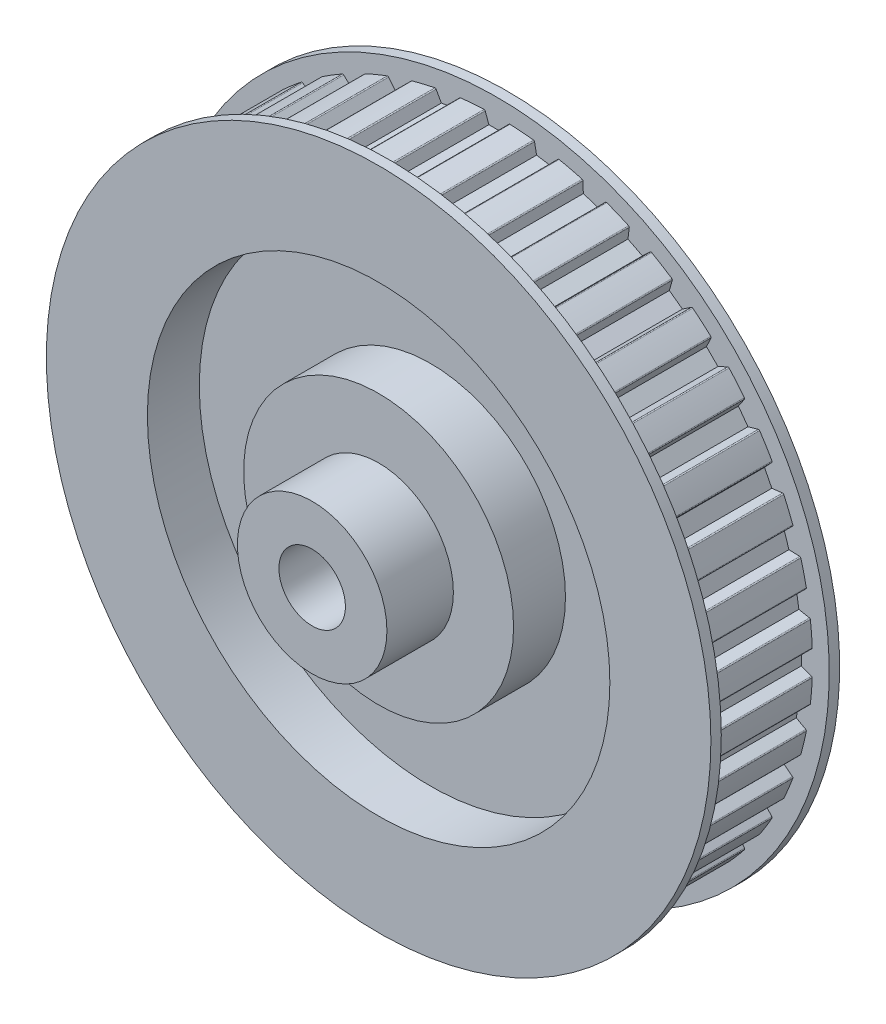
SolidWorks part; units mm, degrees
material "Nylon 101"
ref_plane "Front Plane" through (0, 0, 0) normal (0, 0, 1) x (1, 0, 0)
ref_plane "Top Plane" through (0, 0, 0) normal (0, 1, 0) x (1, 0, 0)
ref_plane "Right Plane" through (0, 0, 0) normal (1, 0, 0) x (0, 0, -1)
sketch "Sketch1" plane through (0, 0, 0) normal (0, 1, 0) x (1, 0, 0)
  line L0 (63.5, -10.3187) -> (0, -10.3187)
  line L1 (0, -10.3187) -> (0, -12.3031)
  line L2 (0, -12.3031) -> (63.5, -12.3031)
  line L3 (63.5, -12.3031) -> (63.5, -10.3187)
  line L4 (0, -10.3187) -> (0, -12.3031) construction
  dimension "D1" = 63.5
  dimension "D2" = 1.9844
revolve "Revolve1" add sketch "Sketch1" angle 360 about L4 reverse direction yes
sketch "Sketch2" plane through (0, 0, 10.3187) normal (0, 0, -1) x (-1, 0, 0)
  line L0 (20.8148, -56.5864) -> (19.4459, -54.8343)
  line L1 (19.4459, -54.8343) -> (16.4988, -55.7919)
  line L2 (16.4988, -55.7919) -> (16.4212, -58.014)
  line L3 (-25.2944, -54.7309) -> (-25.0234, -52.524)
  line L4 (-25.0234, -52.524) -> (-27.7845, -51.1172)
  line L5 (-27.7845, -51.1172) -> (-29.4106, -52.6336)
  line L6 (-52.6336, -29.4106) -> (-51.1172, -27.7845)
  line L7 (-51.1172, -27.7845) -> (-52.524, -25.0234)
  line L8 (-52.524, -25.0234) -> (-54.7309, -25.2944)
  line L9 (-58.014, 16.4212) -> (-55.7919, 16.4988)
  line L10 (-55.7919, 16.4988) -> (-54.8343, 19.4459)
  line L11 (-54.8343, 19.4459) -> (-56.5864, 20.8148)
  line L12 (-37.2822, 47.3848) -> (-35.4389, 46.1414)
  line L13 (-35.4389, 46.1414) -> (-32.9319, 47.9629)
  line L14 (-32.9319, 47.9629) -> (-33.5448, 50.1002)
  line L15 (7.1436, 59.8686) -> (7.5678, 57.686)
  line L16 (7.5678, 57.686) -> (10.6285, 57.2012)
  line L17 (10.6285, 57.2012) -> (11.7064, 59.1459)
  line L18 (40.9692, 44.2358) -> (40.0295, 42.2207)
  line L19 (40.0295, 42.2207) -> (42.2207, 40.0295)
  line L20 (42.2207, 40.0295) -> (44.2358, 40.9692)
  line L21 (59.1459, 11.7064) -> (57.2012, 10.6285)
  line L22 (57.2012, 10.6285) -> (57.686, 7.5678)
  line L23 (57.686, 7.5678) -> (59.8686, 7.1436)
  line L24 (50.1002, -33.5448) -> (47.9629, -32.9319)
  line L25 (47.9629, -32.9319) -> (46.1414, -35.4389)
  line L26 (46.1414, -35.4389) -> (47.3848, -37.2822)
  arc A0 (47.3848, -37.2822) -> (20.8148, -56.5864) centre (0, 0) cw
  arc A1 (16.4212, -58.014) -> (-25.2944, -54.7309) centre (0, 0) cw
  arc A2 (-29.4106, -52.6336) -> (-52.6336, -29.4106) centre (0, 0) cw
  arc A3 (-54.7309, -25.2944) -> (-58.014, 16.4212) centre (0, 0) cw
  arc A4 (-56.5864, 20.8148) -> (-37.2822, 47.3848) centre (0, 0) cw
  arc A5 (-33.5448, 50.1002) -> (7.1436, 59.8686) centre (0, 0) cw
  arc A6 (11.7064, 59.1459) -> (40.9692, 44.2358) centre (0, 0) cw
  arc A7 (44.2358, 40.9692) -> (59.1459, 11.7064) centre (0, 0) cw
  arc A8 (59.8686, 7.1436) -> (50.1002, -33.5448) centre (0, 0) cw
  circle A9 centre (0, 0) radius 63.5 construction
  dimension "D1" = 60.2933
  dimension "D2" = 60.2933
  dimension "D3" = 60.2933
  dimension "D4" = 60.2932
  dimension "D5" = 60.2933
  dimension "D6" = 60.2933
  dimension "D7" = 60.2932
  dimension "D8" = 60.2933
  dimension "D9" = 60.2933
  dimension "D10" = 7.1436
  dimension "D11" = 7.5678
  dimension "D12" = 10.6285
  dimension "D13" = 11.7064
  dimension "D14" = 16.4212
  dimension "D15" = 16.4988
  dimension "D16" = 19.4459
  dimension "D17" = 20.8148
  dimension "D18" = 40.0295
  dimension "D19" = 40.9692
  dimension "D20" = 42.2207
  dimension "D21" = 44.2358
  dimension "D22" = 46.1414
  dimension "D23" = 47.3848
  dimension "D24" = 47.9629
  dimension "D25" = 50.1002
  dimension "D26" = 57.2012
  dimension "D27" = 57.686
  dimension "D28" = 59.1459
  dimension "D29" = 59.8686
  dimension "D30" = 25.0234
  dimension "D31" = 25.2944
  dimension "D32" = 27.7845
  dimension "D33" = 29.4106
  dimension "D34" = 32.9319
  dimension "D35" = 33.5448
  dimension "D36" = 35.4389
  dimension "D37" = 37.2822
  dimension "D38" = 51.1172
  dimension "D39" = 52.524
  dimension "D40" = 52.6336
  dimension "D41" = 54.7309
  dimension "D42" = 54.8343
  dimension "D43" = 55.7919
  dimension "D44" = 56.5864
  dimension "D45" = 58.014
  dimension "D46" = 7.1436
  dimension "D47" = 7.5678
  dimension "D48" = 10.6285
  dimension "D49" = 11.7064
  dimension "D51" = 16.4988
  dimension "D52" = 19.4459
  dimension "D54" = 40.0295
  dimension "D56" = 42.2207
  dimension "D58" = 46.1414
  dimension "D60" = 47.9629
  dimension "D62" = 57.2012
  dimension "D63" = 57.686
  dimension "D66" = 25.0234
  dimension "D68" = 27.7845
  dimension "D70" = 32.9319
  dimension "D72" = 35.4389
  dimension "D74" = 51.1172
  dimension "D75" = 52.524
  dimension "D78" = 54.8343
  dimension "D79" = 55.7919
extrude "Boss-Extrude1" add sketch "Sketch2" along normal blind 20.6375
ref_plane "Plane1" through (0, 0, -10.3187) normal (0, 0, 1) x (1, 0, 0)
sketch "Sketch3" plane through (0, 0, -10.3187) normal (0, 0, 1) x (1, 0, 0)
  circle A0 centre (0, 0) radius 63.5
  dimension "D1" = 127
extrude "Boss-Extrude2" add sketch "Sketch3" against normal blind 1.9844
hole_wizard "Hole1" positions "Sketch5" profile "Sketch4" legacy
sketch "Sketch5" plane through (0, 0, -12.3031) normal (0, 0, -1) x (-1, 0, 0)
  point P0 (0, 0)
sketch "Sketch4" plane through (0, 0, -12.3031) normal (1, 0, 0) x (0, 1, 0)
  line L0 (0, 0) -> (0, 9.9219)
  line L1 (0, 9.9219) -> (44.1912, 9.9219)
  line L2 (44.1912, 9.9219) -> (44.1912, 0)
  line L3 (44.1912, 0) -> (0, 0)
  line L4 (0, 110) -> (0, -10) construction
  dimension "Diameter" = 88.3825
  dimension "Depth" = 9.9219
hole_wizard "Hole2" positions "Sketch7" profile "Sketch6" legacy
sketch "Sketch7" plane through (0, 0, 12.3031) normal (0, 0, 1) x (1, 0, 0)
  point P0 (0, 0)
sketch "Sketch6" plane through (0, 0, 12.3031) normal (1, 0, 0) x (0, -1, 0)
  line L0 (0, 0) -> (0, 9.9219)
  line L1 (0, 9.9219) -> (44.1912, 9.9219)
  line L2 (44.1912, 9.9219) -> (44.1912, 0)
  line L3 (44.1912, 0) -> (0, 0)
  line L4 (0, 110) -> (0, -10) construction
  dimension "Diameter" = 88.3825
  dimension "Depth" = 9.9219
sketch "Sketch8" plane through (0, 0, 0) normal (0, 1, 0) x (1, 0, 0)
  line L0 (14.2875, 12.3031) -> (0, 12.3031)
  line L1 (0, 12.3031) -> (0, 2.3813)
  line L2 (0, 2.3813) -> (14.2875, 2.3813)
  line L3 (14.2875, 2.3813) -> (14.2875, 12.3031)
  line L4 (0, 12.3031) -> (0, 2.3813) construction
  dimension "D1" = 14.2875
  dimension "D2" = 9.9219
revolve "Revolve2" add sketch "Sketch8" angle 360 about L4 reverse direction yes
sketch "Sketch9" plane through (0, 0, 0) normal (0, 1, 0) x (1, 0, 0)
  line L0 (25.7889, -2.3812) -> (0, -2.3813)
  line L1 (0, -2.3813) -> (0, -25.0031)
  line L2 (0, -25.0031) -> (14.2875, -25.0031)
  line L3 (14.2875, -25.0031) -> (14.2875, -12.3031)
  line L4 (14.2875, -12.3031) -> (25.7889, -12.3031)
  line L5 (25.7889, -12.3031) -> (25.7889, -2.3812)
  line L6 (0, -2.3813) -> (0, -25.0031) construction
  dimension "D1" = 14.2875
  dimension "D2" = 25.7889
  dimension "D3" = 12.7
  dimension "D4" = 22.6219
revolve "Revolve3" add sketch "Sketch9" angle 360 about L6 reverse direction yes
hole_wizard "Hole3" positions "Sketch11" profile "Sketch10" legacy
sketch "Sketch11" plane through (0, 0, 25.0031) normal (0, 0, 1) x (1, 0, 0)
  point P0 (0, 0)
sketch "Sketch10" plane through (0, 0, 25.0031) normal (1, 0, 0) x (0, -1, 0)
  line L0 (0, 0) -> (0, 37.3062)
  line L1 (0, 37.3062) -> (6.3564, 37.3062)
  line L2 (6.3564, 37.3062) -> (6.3564, 0)
  line L3 (6.3564, 0) -> (0, 0)
  line L4 (0, 110) -> (0, -10) construction
  dimension "Diameter" = 12.7127
  dimension "Depth" = 37.3062
fillet "Fillet1" radius 0.2286 18 edges at (-7.1436, 59.8686, 0) (58.014, 16.4212, 0) (52.6336, -29.4106, 0) (-59.1459, 11.7064, 0) (37.2822, 47.3848, 0) (-59.8686, 7.1436, 0) (-44.2358, 40.9692, 0) (-50.1002, -33.5448, 0) (54.7309, -25.2944, 0) (-47.3848, -37.2822, 0) (56.5864, 20.8148, 0) (-20.8148, -56.5864, 0) (33.5448, 50.1002, 0) (-16.4212, -58.014, 0) (-11.7064, 59.1459, 0) (25.2944, -54.7309, 0) (-40.9692, 44.2358, 0) (29.4106, -52.6336, 0) tangent propagation no
sketch "Sketch12" plane through (0, 0, -10.3187) normal (0, 0, 1) x (1, 0, 0)
  line L0 (35.4389, 46.1414) -> (37.1438, 47.2914) construction
  line L1 (32.9319, 47.9629) -> (35.4389, 46.1414) construction
  line L2 (33.4987, 49.9397) -> (32.9319, 47.9629) construction
  line L3 (35.4389, 46.1414) -> (37.1438, 47.2914)
  line L4 (32.9319, 47.9629) -> (35.4389, 46.1414)
  line L5 (33.4987, 49.9397) -> (32.9319, 47.9629)
  arc A0 (37.4135, 47.2812) -> (37.1438, 47.2914) centre (37.2716, 47.1019) ccw construction
  arc A1 (33.4987, 49.9397) -> (33.4057, 50.193) centre (33.279, 50.0027) ccw construction
  arc A2 (37.4135, 47.2812) -> (37.1438, 47.2914) centre (37.2716, 47.1019) ccw
  arc A3 (33.4987, 49.9397) -> (33.4057, 50.193) centre (33.279, 50.0027) ccw
  arc A4 (33.4057, 50.193) -> (37.4135, 47.2812) centre (0.056, 0.0771) cw
  dimension "D1" = 60.198
extrude "Cut-Extrude1" cut sketch "Sketch12" along normal blind 20.6502
pattern_circular "CirPattern2" count 40 over 360 about axis through (0, 0, 12.3031) along (0, 0, 1) of "Cut-Extrude1"
equation "\"0.8125in.\"=0.813"
equation "\"D1@Cut-Extrude1\"=\"0.8125in.\""
